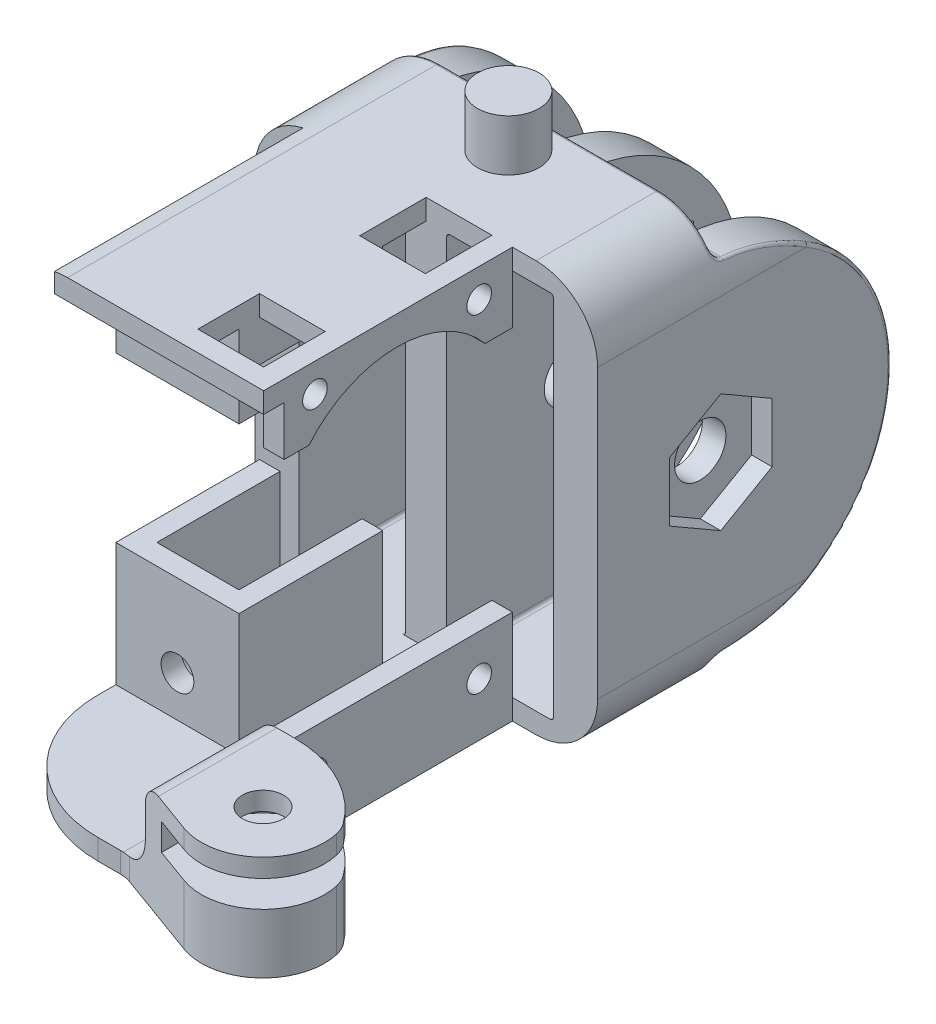
SolidWorks part; units mm, degrees
ref_plane "Front" through (0, 0, 0) normal (0, 0, 1) x (1, 0, 0)
ref_plane "Top" through (0, 0, 0) normal (0, 1, 0) x (1, 0, 0)
ref_plane "Right" through (0, 0, 0) normal (1, 0, 0) x (0, 0, -1)
sketch "Sketch1" plane through (0, 0, 0) normal (0, 0, 1) x (1, 0, 0)
  line L0 (8.35, -10) -> (8.35, 10)
  line L1 (-6.35, -8.5) -> (6.35, -8.5)
  line L2 (-6.35, -8.5) -> (-6.35, 8.5)
  line L3 (-6.35, 8.5) -> (6.35, 8.5)
  line L4 (6.35, -8.5) -> (6.35, 8.5)
  line L7 (-8.35, 10) -> (8.35, 10)
  line L8 (-8.35, -10) -> (-8.35, 10)
  line L9 (-8.35, -10) -> (8.35, -10)
  point P0 (0, 0)
  dimension "D1" = 20
  dimension "D4" = 16.7
extrude "Boss-Extrude1" add sketch "Sketch1" along normal blind 20 and the other way blind 12 contours L1 L4 L3 L2 | L8 L9 L0 L7 L4 L1 L2 L3 region at (0, -9.7394, 0) region at (0, 0, 0)
sketch "Sketch9" plane through (0, 10, 0) normal (0, 1, 0) x (1, 0, 0)
  circle A0 centre (0, 0) radius 1.5
  dimension "D1" = 3
extrude "Boss-Extrude4" add sketch "Sketch9" along normal blind 2.5
sketch "Sketch10" plane through (0, -10, 0) normal (0, -1, 0) x (1, 0, 0)
  circle A0 centre (0, 0) radius 1.5
  dimension "D1" = 3
extrude "Boss-Extrude5" add sketch "Sketch10" along normal blind 2.5 contours A0
sketch "Sketch73" plane through (0, 0, 0) normal (0, 1, 0) x (1, 0, 0)
  line L0 (9.6599, -17.7669) -> (4.8898, -4.6612)
  line L1 (0.0004, 0.0009) -> (0.0004, -19.9991) construction
  line L2 (0.0004, 0.0009) -> (6.8408, -18.7929) construction
  line L3 (5.8148, -21.612) -> (-4.1426, -17.9878)
  arc A0 (0.0004, -19.9991) -> (6.8408, -18.7929) centre (0.0004, 0.0009) ccw construction
  circle A1 centre (6.8408, -18.7929) radius 1
  circle A2 centre (6.8408, -18.7929) radius 3
  circle A3 centre (6.8408, -18.7929) radius 10
  dimension "D1" = 6
  dimension "D2" = 20
  dimension "D3" = 20
extrude "Extrude46" add sketch "Sketch73" along normal blind 10 and the other way blind 10 contours A2 A1 | L0 A3 L3 A2 | A1 region at (2.7313, 0, 14.6834) region at (9.7117, 0, 18.2867) region at (6.8408, 0, 18.7929)
extrude "Extrude52" cut sketch "Sketch" against normal through all both and the other way through all contours A0 A1 L2 | L2 A1 A0 region at (6.8408, 0, 18.7929)
sketch "Sketch" plane through (0, 0, 0) normal (0, 1, 0) x (1, 0, 0) same geometry as "Sketch73"
sketch "Sketch21" plane through (0, 0, 0) normal (1, 0, 0) x (0, 0, -1)
  line L0 (0, 0) -> (2, 0) construction
  line L1 (2, 0) -> (6.3301, 2.5) construction
  circle A0 centre (2, 0) radius 1.25
  circle A1 centre (6.3301, 2.5) radius 1
  circle A2 centre (2, 0) radius 5 construction
  dimension "D1" = 2
  dimension "D2" = 2.5
extrude "Extrude7" cut sketch "Sketch21" against normal through all both and the other way through all contours A0 L0 L1 | L0 A0 L1 region at (0, 0, -2)
sketch "Sketch23" plane through (0, 0, 0) normal (1, 0, 0) x (0, 0, -1)
  line L0 (2, 9.5) -> (2, 10)
  line L2 (2, -8.3) -> (2, -11.4416)
  line L4 (2, 11.5383) -> (19.1929, 11.5383)
  line L6 (2, 11.5383) -> (2, 10)
  line L7 (2, 8.3) -> (2, 9.5)
  line L8 (2, -11.4416) -> (19.1929, -11.4416)
  line L9 (2, -10.6179) -> (2, -8.3)
  line L10 (19.1929, 11.5383) -> (19.1929, -11.4416)
  circle A2 centre (2, 0) radius 4
  arc A4 (2, -8.3) -> (2, 8.3) centre (2, 0) ccw
extrude "Extrude8" cut sketch "Sketch23" against normal through all both and the other way through all contours L2 L6 L0 region at (0, 0.0666, -12.5103)
sketch "Sketch25" plane through (0, 0, 0) normal (1, 0, 0) x (0, 0, -1)
  line L1 (2, 2.8868) -> (-0.5, 1.4434)
  line L2 (-0.5, 1.4434) -> (-0.5, -1.4434)
  line L3 (-0.5, -1.4434) -> (2, -2.8868)
  line L4 (2, -2.8868) -> (4.5, -1.4434)
  line L5 (4.5, -1.4434) -> (4.5, 1.4434)
  line L6 (4.5, 1.4434) -> (2, 2.8868)
  circle A1 centre (2, 0) radius 2.5 construction
  dimension "D1" = 5
extrude "Extrude9" cut sketch "Sketch25" along normal through all from offset 7.35 contours L5 L6 L1 L2 L3 L4 region at (0, 0, -2)
sketch "Sketch74" plane through (0, 0, 0) normal (0, 1, 0) x (1, 0, 0)
  line L0 (0, 0) -> (0, -13.12)
  line L2 (0, -13.12) -> (-35.0583, -13.12)
  line L3 (0, -13.12) -> (0, -42.3661)
  line L4 (0, -42.3661) -> (-35.0583, -42.3661)
  line L5 (-35.0583, -13.12) -> (-35.0583, -42.3661)
extrude "Extrude48" cut sketch "Sketch74" against normal blind 9 and the other way blind 9 contours L2 L5 L4 L3 region at (-17.5292, 0, 27.7431)
sketch "Sketch59" plane through (0, 0, 13.12) normal (0, 0, 1) x (1, 0, 0)
  line L0 (0, 0) -> (-13.8891, 0) construction
  line L13 (0, 0) -> (-3, 0)
  line L14 (-3, 0) -> (-3, -7)
  line L15 (0, 0) -> (0, -1.8329) construction
  line L31 (-3, 0) -> (-3, 7)
  circle A4 centre (-3, -7) radius 0.8
  circle A5 centre (-3, 7) radius 0.8
extrude "Extrude47" cut sketch "Sketch59" against normal through all contours A5 | A4 region at (-2.4503, -6.4503, 13.12) region at (-3.5497, 7.5497, 13.12)
sketch "Sketch75" plane through (0, 0, 0) normal (0, 1, 0) x (1, 0, 0)
  line L0 (0, 0) -> (0, -4)
  line L1 (0, -4) -> (-6, -4)
  line L3 (-6, -4) -> (-15.9073, -4)
  line L4 (-6, -4) -> (-6, -23.9043)
  line L5 (-6, -23.9043) -> (-15.9073, -23.9043)
  line L6 (-15.9073, -4) -> (-15.9073, -23.9043)
  dimension "D1" = 6
  dimension "D2" = 4
extrude "Extrude49" cut sketch "Sketch75" against normal blind 9 and the other way blind 9 contours L3 L6 L5 L4 region at (-10.9536, 0, 13.9522)
sketch "Sketch76" plane through (0, 0, 0) normal (0, 1, 0) x (1, 0, 0)
  line L0 (0, 0) -> (-1, 0)
  line L6 (0, 0) -> (0, 11.9912) construction
  line L12 (0, 0) -> (1, 0)
  line L22 (1, 0) -> (6.2, 0)
  line L23 (1, 0) -> (1, 12.217)
  line L24 (1, 12.217) -> (6.2, 12.217)
  line L25 (6.2, 0) -> (6.2, 12.217)
  line L26 (-1, 0) -> (-6.2, 0)
  line L27 (-1, 0) -> (-1, 13.0329)
  line L28 (-1, 13.0329) -> (-6.2, 13.0329)
  line L29 (-6.2, 0) -> (-6.2, 13.0329)
  line L30 (-1, 0) -> (-6.2, 0)
  line L31 (-1, 0) -> (-1, -6.12)
  line L32 (-1, -6.12) -> (-6.2, -6.12)
  line L33 (-6.2, 0) -> (-6.2, -6.12)
  line L34 (1, 0) -> (6.2, 0)
  line L35 (1, 0) -> (1, -6.12)
  line L36 (1, -6.12) -> (6.2, -6.12)
  line L37 (6.2, 0) -> (6.2, -6.12)
  dimension "D1" = 1
  dimension "D2" = 1
  dimension "D3" = 5.2
  dimension "D4" = 5.2
extrude "Extrude50" cut sketch "Sketch76" against normal blind 9 and the other way blind 9 contours L26 L33 L32 L31 | L29 L26 L27 L28 | L22 L25 L24 L23 | L37 L22 L35 L36 region at (-3.6, 0, 3.06) region at (-3.6, 0, -6.5165) region at (3.6, 0, -6.1085) region at (3.6, 0, 3.06)
sketch "Sketch83" plane through (0, 0, 0) normal (0, 1, 0) x (1, 0, 0)
  line L0 (0, 0) -> (0, -4)
  line L1 (0, 0) -> (0, -6.12)
  line L3 (0, -6.12) -> (2, -6.12)
  line L4 (0, -6.12) -> (0, -4)
  line L5 (0, -4) -> (2, -4)
  line L6 (2, -6.12) -> (2, -4)
  line L7 (0, -6.12) -> (-11.9079, -6.12)
  line L8 (0, -6.12) -> (0, -4)
  line L9 (0, -4) -> (-11.9079, -4)
  line L10 (-11.9079, -6.12) -> (-11.9079, -4)
  dimension "D1" = 4
  dimension "D2" = 2.12
extrude "Extrude56" cut sketch "Sketch83" against normal blind 9 and the other way blind 9 contours L10 L7 L1 L9 | L3 L6 L5 L1 region at (1, 0, 5.06) region at (-5.9539, 0, 5.06)
sketch "Sketch84" plane through (0, 0, 0) normal (0, 1, 0) x (1, 0, 0)
  line L0 (0, 0) -> (0, -6.12)
  line L1 (6.2, -6.12) -> (-6, -6.12) construction
  line L2 (0, -6.12) -> (6.35, -6.12)
  line L4 (0, -6.12) -> (0, -26.7548)
  line L5 (0, -26.7548) -> (2.85, -26.7548)
  line L6 (2.85, -18.793) -> (2.85, -26.7548)
  line L8 (2.85, -15.12) -> (2.85, -18.793)
  line L9 (0, 0) -> (0, -15.12)
  line L10 (2.85, -15.12) -> (6.35, -15.12)
  line L12 (6.35, -6.12) -> (6.35, -15.12)
  dimension "D1" = 6.12
  dimension "D2" = 6.35
  dimension "D3" = 3.5
  dimension "D4" = 9
extrude "Extrude57" cut sketch "Sketch84" against normal blind 9 and the other way blind 9 contours L2 L4 L5 L6 region at (2.5324, 0, 14.4083)
sketch "Sketch85" plane through (0, 0, 6.12) normal (0, 0, -1) x (-1, 0, 0)
  line L0 (1, 7) -> (0, 7)
  line L1 (0, 9) -> (0, -9) construction
  line L2 (0, 7) -> (0, 0)
  line L3 (0, 0) -> (6, 0)
  line L4 (6, 9) -> (6, -9) construction
  line L5 (6, 0) -> (6, 7)
  line L6 (6, 7) -> (5, 7)
  line L7 (1, -7) -> (1, -3)
  line L8 (1, -3) -> (0, -3)
  line L9 (0, -3) -> (0, 0)
  line L10 (5, -7) -> (5, -3)
  line L11 (5, -3) -> (6, -3)
  line L12 (6, -3) -> (6, 0)
  circle A0 centre (3, -7) radius 2
  circle A1 centre (3, 7) radius 2
  circle M1 centre (3, -7) radius 0.8
  circle M2 centre (3, 7) radius 0.8
  line M3 (0, 9) -> (0, -9)
  line M5 (6, -9) -> (6, 9)
extrude "Extrude58" cut sketch "Sketch85" against normal blind 6 contours A0 L10 L11 L3 L8 L7 M5 M3 | A1 L0 L3 L6 M3 M5 | A1 M2 | A0 M1 region at (-3, 3.0336, 6.12) region at (-3, 8.9434, 6.12) region at (-3, -2.466, 6.12) region at (-3, -5.0566, 6.12)
sketch "Sketch86" plane through (0, 0, 12.12) normal (0, 0, -1) x (-1, 0, 0)
  line L1 (0, 0) -> (6, 0)
  line L2 (0, 0) -> (0, -3)
  line L3 (0, -3) -> (6, -3)
  line L4 (6, 0) -> (6, -3)
  line L5 (0, 0) -> (6, 0)
  line L6 (0, 0) -> (0, 5)
  line L7 (0, 5) -> (6, 5)
  line L8 (6, 0) -> (6, 5)
  line M12 (5, -3) -> (6, -3)
  line M13 (6, -3) -> (6, 7)
  line M17 (0, 7) -> (0, -3)
  line M18 (0, -3) -> (1, -3)
extrude "Extrude59" cut sketch "Sketch86" against normal blind 1 contours L3 L1 M18 M12 M13 M17 | L7 L1 M17 M13 region at (-3, 2.5, 12.12) region at (-3, -1.5, 12.12)
sketch "Sketch87" plane through (0, 0, 0) normal (0, 0, 1) x (1, 0, 0)
  line L0 (0, 0) -> (0, 2.5)
  line L2 (0, 2.5) -> (15, 2.5)
  line L3 (0, 2.5) -> (0, 9)
  line L4 (0, 9) -> (15, 9)
  line L5 (15, 2.5) -> (15, 9)
  line L6 (0, 2.5) -> (15, 2.5)
  line L7 (0, 2.5) -> (0, -4.9)
  line L8 (0, -4.9) -> (15, -4.9)
  line L9 (15, 2.5) -> (15, -4.9)
  dimension "D1" = 2.5
  dimension "D2" = 6.5
  dimension "D3" = 7.4
extrude "Extrude60" cut sketch "Sketch87" along normal through all from offset 4 contours L9 L2 L0 L7 L8 | L2 L5 L4 L3 region at (7.5, -1.2, 0) region at (7.5, 5.75, 0)
sketch "Sketch89" plane through (0, 0, 0) normal (1, 0, 0) x (0, 0, -1)
  line L0 (0, 0) -> (0, 5.4564) construction
  line L1 (2, 0) -> (2, 4.1188) construction
  line L2 (2, 0) -> (-1002.016, 0) construction
  line L3 (-9.62, 3) -> (-9.62, -6.2769) construction
  line L4 (-5.62, 3) -> (-13.62, 3)
  line L5 (-13.62, 3) -> (-13.62, 8.6)
  line L6 (-13.62, 3) -> (-13.62, -7.4)
  line L7 (-5.62, 3) -> (-5.62, -7.4)
  line L8 (-5.62, 3) -> (-5.62, 8.6)
  circle A0 centre (-9.62, 3) radius 1.5
  dimension "D1" = 10.4
  dimension "D2" = 5.6
  dimension "D3" = 4
sketch "Sketch90" plane through (0, 0, 0) normal (1, 0, 0) x (0, 0, -1)
  line L1 (-9.62, 3) -> (-15.12, 3)
  line L2 (-9.62, 3) -> (-9.62, 13)
  line L3 (-9.62, 13) -> (-15.12, 13)
  line L4 (-15.12, 3) -> (-15.12, 13)
  line L5 (-9.62, 3) -> (-4, 3)
  line L6 (-9.62, 3) -> (-9.62, 13)
  line L7 (-9.62, 13) -> (-4, 13)
  line L8 (-4, 3) -> (-4, 13)
  line L9 (-9.62, 3) -> (-15.12, 3)
  line L10 (-9.62, 3) -> (-9.62, -12)
  line L11 (-9.62, -12) -> (-15.12, -12)
  line L12 (-15.12, 3) -> (-15.12, -12)
  line L13 (-9.62, 3) -> (-4, 3)
  line L14 (-9.62, 3) -> (-9.62, -12)
  line L15 (-9.62, -12) -> (-4, -12)
  line L16 (-4, 3) -> (-4, -12)
  dimension "D1" = 5.5
  dimension "D2" = 5.62
extrude "Extrude61" cut sketch "Sketch90" along normal through all from offset 4.2 contours L4 L1 L2 L3 | L5 L8 L7 L2 | L1 L12 L11 L10 | L16 L5 L10 L14 L15 region at (0, -4.5, 12.37) region at (0, 8, 12.37) region at (0, 8, 6.81) region at (0, -4.5, 6.81)
sketch "Sketch92" plane through (0, 0, 0) normal (1, 0, 0) x (0, 0, -1)
  line L1 (-15.12, 10) -> (-4, 10)
  line L2 (-15.12, 10) -> (-15.12, -10)
  line L3 (-15.12, -10) -> (-4, -10)
  line L4 (-4, 10) -> (-4, -10)
extrude "Extrude62" add sketch "Sketch92" against normal blind 1 from offset 4.2
sketch "Sketch93" plane through (0, 0, 0) normal (1, 0, 0) x (0, 0, -1)
  circle A0 centre (-13.62, 8.6) radius 0.6
  circle A1 centre (-5.62, 8.6) radius 0.6
  circle A2 centre (-5.62, -7.4) radius 0.6
  circle A3 centre (-13.62, -7.4) radius 0.6
extrude "Extrude63" cut sketch "Sketch93" against normal blind 2 from offset 4.2
sketch "Sketch96" plane through (0, 0, 0) normal (1, 0, 0) x (0, 0, -1)
  line L1 (-12.12, 6.6) -> (-15.12, 6.6)
  line L2 (-12.12, 6.6) -> (-12.12, 10.6)
  line L3 (-12.12, 10.6) -> (-15.12, 10.6)
  line L4 (-15.12, 6.6) -> (-15.12, 10.6)
  line L5 (-12.12, 6.6) -> (-15.12, 10.6) construction
  line L6 (-12.12, 10.6) -> (-15.12, 6.6) construction
  line L7 (-7.24, 6.6) -> (-4, 6.6)
  line L8 (-7.24, 6.6) -> (-7.24, 10.6)
  line L9 (-7.24, 10.6) -> (-4, 10.6)
  line L10 (-4, 6.6) -> (-4, 10.6)
  line L11 (-7.24, 6.6) -> (-4, 10.6) construction
  line L12 (-7.24, 10.6) -> (-4, 6.6) construction
  line L13 (-12.12, -12.4) -> (-15.12, -12.4)
  line L14 (-12.12, -12.4) -> (-12.12, -2.4)
  line L15 (-12.12, -2.4) -> (-15.12, -2.4)
  line L16 (-15.12, -12.4) -> (-15.12, -2.4)
  line L17 (-12.12, -12.4) -> (-15.12, -2.4) construction
  line L18 (-12.12, -2.4) -> (-15.12, -12.4) construction
  line L19 (-4, -12.4) -> (-7.24, -12.4)
  line L20 (-4, -12.4) -> (-4, -2.4)
  line L21 (-4, -2.4) -> (-7.24, -2.4)
  line L22 (-7.24, -12.4) -> (-7.24, -2.4)
  line L23 (-4, -12.4) -> (-7.24, -2.4) construction
  line L24 (-4, -2.4) -> (-7.24, -12.4) construction
  point P0 (-13.62, 8.6)
  point P6 (-5.62, 8.6)
  point P12 (-13.62, -7.4)
  point P18 (-5.62, -7.4)
  dimension "D1" = 3
  dimension "D2" = 4
  dimension "D3" = 3.24
  dimension "D4" = 4
  dimension "D5" = 3
  dimension "D6" = 10
  dimension "D7" = 3.24
  dimension "D8" = 10
extrude "Extrude64" cut sketch "Sketch96" against normal blind 3.2 from offset 3.2
sketch "Sketch97" plane through (0, 0, 0) normal (1, 0, 0) x (0, 0, -1)
  line L0 (-5.62, 3) -> (-13.62, 3) construction
  line L1 (-9.62, 3) -> (-9.62, 6.6)
  line L2 (0, 0) -> (-1.1503, 0) construction
  line L3 (-9.62, 6.6) -> (-4, 6.6)
  line L4 (-4, -9) -> (-4, 9) construction
  line L5 (-4, 6.6) -> (-4, -11.5902)
  line L6 (-9.62, 6.6) -> (-15.12, 6.6)
  line L7 (-15.12, 9) -> (-15.12, -4.9) construction
  line L8 (-15.12, 6.6) -> (-15.12, -12.9504)
  line L9 (-9.62, 3) -> (-9.62, -5.4)
  line L10 (0, 0) -> (0, 6.2221) construction
  line L11 (-9.62, -5.4) -> (-15.12, -5.4)
  line L12 (-9.62, -5.4) -> (-4, -5.4)
  line L13 (2, 0) -> (2, 5.7085) construction
  circle A1 centre (-9.62, 3) radius 5.6
extrude "Extrude65" cut sketch "Sketch97" against normal blind 1 from offset 4.2 contours A1 L8 L11 L9 | A1 L9 L12 L5 L3 | L9 A1 L3 L1 | L6 A1 L8 L9 L1 | L3 A1 L6 | A1 L6 L8 region at (0, 2.3904, 12.086) region at (0, 2.3924, 7.144) region at (0, 7.4137, 9.62) region at (0, -2.6149, 6.211) region at (0, -3.2628, 12.8039) region at (0, 5.8626, 14.7552)
sketch "Sketch98" plane through (0, 0, 0) normal (0, 1, 0) x (1, 0, 0)
  line L0 (4.0908, -18.7929) -> (4.0908, -22.9688)
  line L1 (6.8408, -16.0429) -> (11.0167, -16.0429)
  circle A0 centre (6.8408, -18.7929) radius 2.75
  arc A1 (4.0908, -22.9688) -> (11.0167, -16.0429) centre (6.8408, -18.7929) ccw
  dimension "D1" = 5
  dimension "D2" = 5.5
extrude "Extrude66" cut sketch "Sketch98" along normal blind 1.2 and the other way blind 0.1 from offset 7 contours L0 A1 L1 A0 | A0 region at (6.8408, 0, 21.6526) region at (6.8408, 0, 18.7929) offset against normal yes
sketch "Sketch99" plane through (0, 0, 0) normal (0, 1, 0) x (1, 0, 0)
  line L0 (-6.35, -4) -> (-6, -4)
  line L1 (0, 0) -> (-6.35, 0)
  line L2 (-6.35, 0) -> (-6.35, -4)
  line L3 (-6, -4) -> (-6, -22.0258)
  line L4 (-6, -22.0258) -> (-14.9452, -22.0258)
  line L5 (-14.9452, -22.0258) -> (-14.9452, -4)
  line L6 (-14.9452, -4) -> (-6.35, -4)
extrude "Extrude67" cut sketch "Sketch99" along normal through all and the other way through all contours L6 L5 L4 L3 L0 region at (-10.4726, 0, 13.0129)
sketch "Sketch102" plane through (0, 0, 0) normal (1, 0, 0) x (0, 0, -1)
  line L1 (2, 0) -> (6.3301, 2.5) construction
  circle A0 centre (2, 0) radius 1.25
  circle A1 centre (6.3301, 2.5) radius 1
  circle A2 centre (2, 0) radius 5 construction
  dimension "D1" = 2
  dimension "D2" = 2.5
extrude "Extrude70" cut sketch "Sketch102" against normal through all and the other way blind 2
fillet "Fillet1" radius 3 4 edges at (-8.35, -10, 1) (8.35, -10, 1) (-8.35, 10, 1) (8.35, 10, 1)
fillet "Fillet2" radius 0.4 6 edges at (0, -8.3, -2) (7.1269, 8.3, -2) (7.1269, -8.3, -2) (-7.1269, -8.3, -2) (-7.1269, 8.3, -2) (0, 8.3, -2)
fillet "Fillet3" radius 0.16 8 edges at (1, -9, 1) (-1, -9, 1) (6.2, 9, 1) (-1, 9, 1) (1, 9, 1) (-6.2, 9, 1) (-6.2, -9, 1) (6.2, -9, 1)
fillet "Fillet4" radius 0.16 16 edges at (8.1751, -8.0093, -4.1776) (6.7514, -9.6526, -2) (0, -10, -2) (-6.7514, -9.6526, -2) (-8.2111, -7.9022, -4.5389) (-8.35, 0, -10.3) (-8.1751, 8.0093, -4.1776) (-6.7514, 9.6526, -2) (0, 10, -2) (6.7514, 9.6526, -2) (8.0164, 8.3749, -2.1546) (8.2111, 7.9022, -4.5389) (8.35, 0, -10.3) (7.9975, -8.411, -2.1142) (-8.0164, -8.3749, -2.1546) (-7.9975, 8.411, -2.1142)
sketch "Sketch104" plane through (0, 0, 0) normal (0, 1, 0) x (1, 0, 0)
  line L0 (0, 0) -> (0, -16.12)
  line L2 (0, -16.12) -> (-13.0823, -16.12)
  line L3 (0, -16.12) -> (0, -21.4119)
  line L4 (0, -21.4119) -> (-13.0823, -21.4119)
  line L5 (-13.0823, -16.12) -> (-13.0823, -21.4119)
  line L6 (0, -16.12) -> (4.2, -16.12)
  line L7 (0, -16.12) -> (0, -22.7033)
  line L8 (0, -22.7033) -> (4.2, -22.7033)
  line L9 (4.2, -16.12) -> (4.2, -22.7033)
  line L10 (4.2, -16.12) -> (14.8583, -16.12)
  line L11 (4.2, -16.12) -> (4.2, -11.241)
  line L12 (4.2, -11.241) -> (14.8583, -11.241)
  line L13 (14.8583, -16.12) -> (14.8583, -11.241)
  line L14 (4.2, -16.12) -> (15.7844, -16.12)
  line L15 (4.2, -16.12) -> (4.2, -24.1026)
  line L16 (4.2, -24.1026) -> (15.7844, -24.1026)
  line L17 (15.7844, -16.12) -> (15.7844, -24.1026)
extrude "Extrude72" cut sketch "Sketch104" along normal through all contours L2 L5 L4 L3 | L9 L6 L3 L7 L8 | L17 L14 L10 L9 L15 L16 | L10 L13 L12 L11 region at (-6.5411, 0, 18.7659) region at (2.1, 0, 19.4117) region at (9.9922, 0, 20.1113) region at (9.5292, 0, 13.6805)
sketch "Sketch103" plane through (0, -10, 0) normal (0, -1, 0) x (1, 0, 0)
  line L1 (6.8408, 20.7559) -> (5.1408, 19.7744)
  line L2 (5.1408, 19.7744) -> (5.1408, 17.8115)
  line L3 (5.1408, 17.8115) -> (6.8408, 16.83)
  line L4 (6.8408, 16.83) -> (8.5408, 17.8115)
  line L5 (8.5408, 17.8115) -> (8.5408, 19.7744)
  line L6 (8.5408, 19.7744) -> (6.8408, 20.7559)
  circle A0 centre (6.8408, 18.7929) radius 1.7 construction
extrude "Extrude71" cut sketch "Sketch103" against normal blind 2.5
fillet "Fillet8" radius 6 1 edges at (-6, -9.4644, 20)
fillet "Fillet9" radius 1.6 1 edges at (1.3858, -9.5, 20)
fillet "Fillet10" radius 1.6 1 edges at (2.85, -9, 17.8265)
fillet "Fillet11" radius 1 1 edges at (2.85, -4.9, 17.8265)
sketch "Sketch105" plane through (1, 0, 0) normal (1, 0, 0) x (0, 0, -1)
  line L1 (6.3301, 4.463) -> (4.6301, 3.4815)
  line L2 (4.6301, 3.4815) -> (4.6301, 1.5185)
  line L3 (4.6301, 1.5185) -> (6.3301, 0.537)
  line L4 (6.3301, 0.537) -> (8.0301, 1.5185)
  line L5 (8.0301, 1.5185) -> (8.0301, 3.4815)
  line L6 (8.0301, 3.4815) -> (6.3301, 4.463)
  circle A0 centre (6.3301, 2.5) radius 1.7 construction
  dimension "D1" = 3.4
extrude "Extrude73" cut sketch "Sketch105" against normal blind 1.5
sketch "Sketch106" plane through (0, 0, 0) normal (1, 0, 0) x (0, 0, -1)
  circle A0 centre (6.3301, 2.5) radius 1.7
  dimension "D1" = 3.4
extrude "Extrude74" cut sketch "Sketch106" against normal through all from offset 7.35 offset against normal yes
fillet "Fillet12" radius 6 1 edges at (8.6965, -7.45, 15.12)
fillet "Fillet13" radius 1.6 2 edges at (9.6599, -8.55, 17.7669) (9.6599, -5.35, 17.7669)
sketch "Sketch109" plane through (0, 0, 0) normal (1, 0, 0) x (0, 0, -1)
  circle A0 centre (2, 0) radius 2.5
  dimension "D1" = 5
extrude "Extrude75" cut sketch "Sketch109" against normal through all from offset 7.35 offset against normal yes
